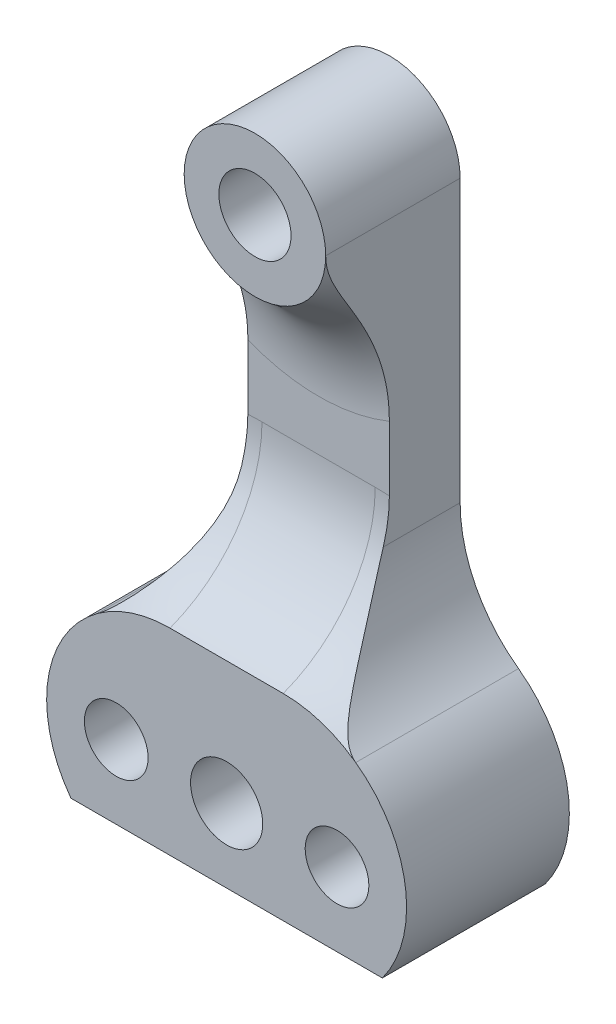
SolidWorks part; units mm, degrees
other "Markup1"
sketch "Sketch13" plane through (12.7171, -43.7171, 0) normal (0.5134, -0.2041, -0.8335) x (-0.7483, -0.582, -0.3184)
ref_plane "Front Plane" through (0, 0, 0) normal (0, 0, 1) x (1, 0, 0)
ref_plane "Top Plane" through (0, 0, 0) normal (0, 1, 0) x (1, 0, 0)
ref_plane "Right Plane" through (0, 0, 0) normal (1, 0, 0) x (0, 0, -1)
sketch "Sketch1" plane through (0, 0, 0) normal (0, 0, 1) x (1, 0, 0)
  line L2 (-4, 0) -> (-4, -35)
  line L4 (4, 0) -> (4, -35)
  arc A3 (4, 0) -> (-4, 0) centre (0, 0) ccw
  arc A4 (-4, -35) -> (4, -35) centre (0, -35) ccw
  dimension "D1" = 35
  dimension "D2" = 4
extrude "Boss-Extrude1" add sketch "Sketch1" along normal blind 5
ref_plane "Plane1" through (0, 0, 5) normal (0, 0, 1) x (1, 0, 0)
sketch "Sketch2" plane through (0, 0, 5) normal (0, 0, 1) x (1, 0, 0)
  circle A0 centre (0, 0) radius 2.55
  circle A1 centre (0, -35) radius 2.55
  arc A2 (-4, -35) -> (4, -35) centre (0, -35) ccw construction
  dimension "D2" = 5.1
extrude "Cut-Extrude1" cut sketch "Sketch2" against normal through all
ref_plane "Plane2" through (0, 0, 5) normal (0, 0, 1) x (1, 0, 0)
sketch "Sketch3" plane through (0, 0, 5) normal (0, 0, 1) x (1, 0, 0)
  line L0 (4, -17.5) -> (-4, -17.5) construction
  line L1 (4, -35) -> (4, 0) construction
  line L2 (-4, 0) -> (-4, -35) construction
  circle A0 centre (0, -35) radius 4
  circle A1 centre (0, 0) radius 4
extrude "Boss-Extrude2" add sketch "Sketch3" along normal blind 6.5
ref_plane "Plane3" through (0, 0, 0) normal (0, 0, -1) x (-1, 0, 0)
sketch "Sketch4" plane through (0, 0, 0) normal (0, 0, -1) x (-1, 0, 0)
  line L0 (-4, -17.5) -> (4, -17.5) construction
  line L1 (-4, -35) -> (-4, 0) construction
  line L2 (4, 0) -> (4, -35) construction
  circle A0 centre (0, -35) radius 2.55
  circle A1 centre (0, -35) radius 2.55 construction
  circle A2 centre (0, 0) radius 2.55
extrude "Cut-Extrude2" cut sketch "Sketch4" against normal through all
ref_plane "Plane4" through (0, 0, 11.5) normal (0, 0, 1) x (1, 0, 0)
sketch "Sketch5" plane through (0, 0, 11.5) normal (0, 0, 1) x (1, 0, 0)
  circle A0 centre (0, 0) radius 4
extrude "Cut-Extrude3" cut sketch "Sketch5" against normal blind 2
ref_plane "Plane5" through (0, 0, 11.5) normal (0, 0, 1) x (1, 0, 0)
sketch "Sketch6" plane through (0, 0, 11.5) normal (0, 0, 1) x (1, 0, 0)
  line L0 (-4, -35) -> (4, -35) construction
  line L1 (-4, -26.2829) -> (4, -26.2829)
  line L3 (-11.0026, -40.1915) -> (11.0026, -40.1915)
  circle A1 centre (0, -35) radius 2.55
  circle A2 centre (0, -35) radius 2.55 construction
  circle A3 centre (0, -35) radius 4 construction
  arc A4 (-4, -26.2829) -> (-11.0026, -40.1915) centre (-4, -35) ccw
  arc A5 (11.0026, -40.1915) -> (4, -26.2829) centre (4, -35) ccw
  point P11 (0, -35)
extrude "Boss-Extrude3" add sketch "Sketch6" against normal up to surface (11.5 mm away) up to face at (2.55, 0, 0)
ref_plane "Plane7" through (0, 0, 0) normal (0, 0, -1) x (-1, 0, 0)
sketch "Sketch9" plane through (0, 0, 0) normal (0, 0, -1) x (-1, 0, 0)
  line L0 (0, -35) -> (50000, -35) construction
  line L1 (0, -35) -> (0, -26.1194) construction
  point P11 (7.8, -35)
  point P12 (-7.8, -35)
ref_plane "Plane9" through (0, 0, 0) normal (0, 0, -1) x (-1, 0, 0)
sketch "Sketch11" plane through (0, 0, 0) normal (0, 0, -1) x (-1, 0, 0)
  line L0 (-5, 0) -> (-5, -30.9813)
  line L1 (5, 0) -> (5, -30.9813)
  line L2 (5, -30.9813) -> (-5, -30.9813)
  arc A0 (5, 0) -> (-5, 0) centre (0, 0) ccw
  circle A3 centre (0, 0) radius 2.55
  circle A4 centre (0, 0) radius 2.55 construction
  dimension "D1" = 10
extrude "Boss-Extrude4" add sketch "Sketch11" against normal up to surface (5 mm away) up to face at (0, -14.1414, 5)
ref_plane "Plane10" through (0, 0, 9.5) normal (0, 0, 1) x (1, 0, 0)
sketch "Sketch12" plane through (0, 0, 9.5) normal (0, 0, 1) x (1, 0, 0)
  circle A0 centre (0, 0) radius 2.55
  circle A1 centre (0, 0) radius 5
  circle A2 centre (0, 0) radius 2.55 construction
extrude "Boss-Extrude5" add sketch "Sketch12" against normal up to surface (4.5 mm away) up to face at (0, -16.703, 5)
ref_plane "Plane11" through (0, 0, 0) normal (0, 0, -1) x (-1, 0, 0)
fillet "Fillet1" radius 10 2 edges at (5, -26.3404, 2.5) (-5, -26.3404, 2.5)
fillet "Fillet2" radius 10 3 edges at (6.6933, -26.7094, 5) (-6.6933, -26.7094, 5) (0, -26.2829, 5)
fillet "Fillet3" radius 10 1 edges at (0, -5, 5)
hole_wizard "CBORE for M4 SHCS1" positions "Sketch14" profile "Sketch15" counterbore size "M4" standard "ANSI Metric" end condition up to next
sketch "Sketch14" plane through (0, 0, 0) normal (0, 0, -1) x (-1, 0, 0)
  point P0 (7.8, -35)
  point P3 (-7.8, -35)
sketch "Sketch15" plane through (-7.8, -35, 0) normal (1, 0, 0) x (0, 1, 0)
  line L0 (0, 0) -> (0, 11.5)
  line L1 (0, 11.5) -> (2.25, 11.5)
  line L3 (2.25, 11.5) -> (2.25, 4)
  line L4 (2.25, 4) -> (4, 4)
  line L5 (4, 4) -> (4, 0)
  line L7 (4, 0) -> (0, 0)
  line L11 (0, -6.35) -> (0, 107.95) construction
  dimension "Thru Hole Dia." = 4.5
  dimension "Thru Hole Depth" = 11.5
  dimension "C'Bore Dia." = 8
  dimension "C'Bore Depth" = 4
